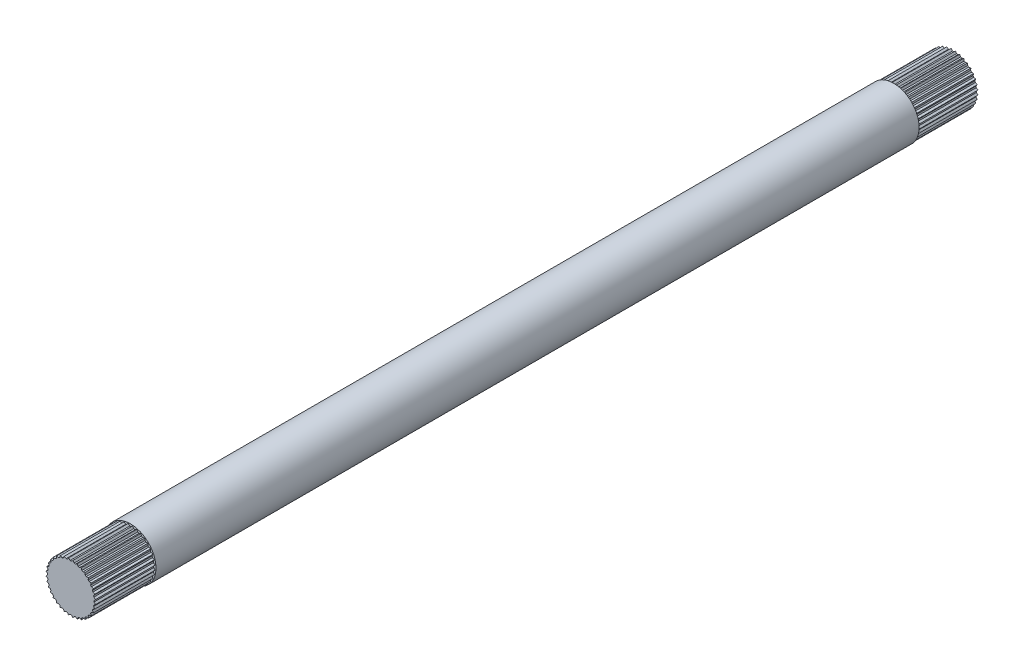
SolidWorks part; units mm, degrees
material "AISI 1015 Steel, Cold Drawn (SS)"
ref_plane "X-Y Datum" through (0, 0, 0) normal (0, 0, 1) x (1, 0, 0)
ref_plane "X-Z Datum" through (0, 0, 0) normal (0, 1, 0) x (1, 0, 0)
ref_plane "Y-Z Datum" through (0, 0, 0) normal (1, 0, 0) x (0, 0, -1)
sketch "Sketch9" plane through (0, 0, 0) normal (0, 1, 0) x (1, 0, 0)
  line L0 (16.002, 0) -> (0, 0)
  line L1 (0, 0) -> (0, -389.0916)
  line L2 (0, -389.0916) -> (-72.2493, -524.9728)
  dimension "D1" = 153.895
  dimension "D2" = 28
  dimension "D3" = 389.0916
  dimension "D5" = 16.002
sketch "Sketch5" plane through (0, 0, 0) normal (0, 1, 0) x (1, 0, 0)
  line L0 (7.9375, -350.9916) -> (7.9375, -22.1615)
  line L1 (7.9375, -22.1615) -> (9.525, -22.1615)
  line L2 (9.525, -22.1615) -> (9.525, -350.9916)
  line L3 (9.525, -350.9916) -> (7.9375, -350.9916)
  line L5 (16.002, 0) -> (0, 0) construction
  line L6 (0, 0) -> (0, -389.0916) construction
  line L7 (0, -389.0916) -> (9.525, -389.0916) construction
  line L8 (12.5602, -369.8416) -> (0, -369.8416) construction
  dimension "D1" = 1.5875
  dimension "D2" = 22.1615
  dimension "D3" = 7.9375
  dimension "D4" = 19.25
  dimension "D5" = 38.1
revolve "Revolve2" add sketch "Sketch5" angle 360 about L1
sketch "Sketch6" plane through (0, 0, 0) normal (0, 1, 0) x (1, 0, 0)
  circle A0 centre (0, -33.1635) radius 1.5875 construction
  circle A1 centre (0, -33.1635) radius 1.5875
sketch "Sketch7" plane through (0, 0, 0) normal (1, 0, 0) x (0, 0, -1)
  circle A2 centre (-39.196, 0) radius 1.5875
  circle A4 centre (-39.196, 0) radius 1.5875 construction
extrude "Cut-Extrude5" [suppressed] cut sketch "Sketch7" against normal through all both and the other way through all
extrude "Cut-Extrude6" [suppressed] cut sketch "Sketch6" against normal through all both and the other way through all
sketch "Sketch8" plane through (0, 0, 0) normal (0, 0, 1) x (1, 0, 0)
  line L0 (9.2357, -0.808) -> (8.6817, -0.254)
  line L1 (8.6817, -0.254) -> (8.6817, 0.254)
  line L2 (8.6817, 0.254) -> (9.2357, 0.808)
  line L3 (8.6817, 0) -> (0, 0) construction
  line L4 (8.9551, -2.3995) -> (8.5057, -1.7577)
  line L5 (8.5057, -1.7577) -> (8.5939, -1.2574)
  line L6 (8.5939, -1.2574) -> (9.2357, -0.808)
  line L7 (8.4024, -3.9181) -> (8.0713, -3.208)
  line L8 (8.0713, -3.208) -> (8.245, -2.7306)
  line L9 (8.245, -2.7306) -> (8.9551, -2.3995)
  line L10 (7.5944, -5.3176) -> (7.3916, -4.5608)
  line L11 (7.3916, -4.5608) -> (7.6456, -4.1209)
  line L12 (7.6456, -4.1209) -> (8.4024, -3.9181)
  line L13 (6.5556, -6.5556) -> (6.4873, -5.7751)
  line L14 (6.4873, -5.7751) -> (6.8138, -5.3859)
  line L15 (6.8138, -5.3859) -> (7.5944, -5.3176)
  line L16 (5.3176, -7.5944) -> (5.3859, -6.8138)
  line L17 (5.3859, -6.8138) -> (5.7751, -6.4873)
  line L18 (5.7751, -6.4873) -> (6.5556, -6.5556)
  line L19 (3.9181, -8.4024) -> (4.1209, -7.6456)
  line L20 (4.1209, -7.6456) -> (4.5608, -7.3916)
  line L21 (4.5608, -7.3916) -> (5.3176, -7.5944)
  line L22 (2.3995, -8.9551) -> (2.7306, -8.245)
  line L23 (2.7306, -8.245) -> (3.208, -8.0713)
  line L24 (3.208, -8.0713) -> (3.9181, -8.4024)
  line L25 (0.808, -9.2357) -> (1.2574, -8.5939)
  line L26 (1.2574, -8.5939) -> (1.7577, -8.5057)
  line L27 (1.7577, -8.5057) -> (2.3995, -8.9551)
  line L28 (-0.808, -9.2357) -> (-0.254, -8.6817)
  line L29 (-0.254, -8.6817) -> (0.254, -8.6817)
  line L30 (0.254, -8.6817) -> (0.808, -9.2357)
  line L31 (-2.3995, -8.9551) -> (-1.7577, -8.5057)
  line L32 (-1.7577, -8.5057) -> (-1.2574, -8.5939)
  line L33 (-1.2574, -8.5939) -> (-0.808, -9.2357)
  line L34 (-3.9181, -8.4024) -> (-3.208, -8.0713)
  line L35 (-3.208, -8.0713) -> (-2.7306, -8.245)
  line L36 (-2.7306, -8.245) -> (-2.3995, -8.9551)
  line L37 (-5.3176, -7.5944) -> (-4.5608, -7.3916)
  line L38 (-4.5608, -7.3916) -> (-4.1209, -7.6456)
  line L39 (-4.1209, -7.6456) -> (-3.9181, -8.4024)
  line L40 (-6.5556, -6.5556) -> (-5.7751, -6.4873)
  line L41 (-5.7751, -6.4873) -> (-5.3859, -6.8138)
  line L42 (-5.3859, -6.8138) -> (-5.3176, -7.5944)
  line L43 (-7.5944, -5.3176) -> (-6.8138, -5.3859)
  line L44 (-6.8138, -5.3859) -> (-6.4873, -5.7751)
  line L45 (-6.4873, -5.7751) -> (-6.5556, -6.5556)
  line L46 (-8.4024, -3.9181) -> (-7.6456, -4.1209)
  line L47 (-7.6456, -4.1209) -> (-7.3916, -4.5608)
  line L48 (-7.3916, -4.5608) -> (-7.5944, -5.3176)
  line L49 (-8.9551, -2.3995) -> (-8.245, -2.7306)
  line L50 (-8.245, -2.7306) -> (-8.0713, -3.208)
  line L51 (-8.0713, -3.208) -> (-8.4024, -3.9181)
  line L52 (-9.2357, -0.808) -> (-8.5939, -1.2574)
  line L53 (-8.5939, -1.2574) -> (-8.5057, -1.7577)
  line L54 (-8.5057, -1.7577) -> (-8.9551, -2.3995)
  line L55 (-9.2357, 0.808) -> (-8.6817, 0.254)
  line L56 (-8.6817, 0.254) -> (-8.6817, -0.254)
  line L57 (-8.6817, -0.254) -> (-9.2357, -0.808)
  line L58 (-8.9551, 2.3995) -> (-8.5057, 1.7577)
  line L59 (-8.5057, 1.7577) -> (-8.5939, 1.2574)
  line L60 (-8.5939, 1.2574) -> (-9.2357, 0.808)
  line L61 (-8.4024, 3.9181) -> (-8.0713, 3.208)
  line L62 (-8.0713, 3.208) -> (-8.245, 2.7306)
  line L63 (-8.245, 2.7306) -> (-8.9551, 2.3995)
  line L64 (-7.5944, 5.3176) -> (-7.3916, 4.5608)
  line L65 (-7.3916, 4.5608) -> (-7.6456, 4.1209)
  line L66 (-7.6456, 4.1209) -> (-8.4024, 3.9181)
  line L67 (-6.5556, 6.5556) -> (-6.4873, 5.7751)
  line L68 (-6.4873, 5.7751) -> (-6.8138, 5.3859)
  line L69 (-6.8138, 5.3859) -> (-7.5944, 5.3176)
  line L70 (-5.3176, 7.5944) -> (-5.3859, 6.8138)
  line L71 (-5.3859, 6.8138) -> (-5.7751, 6.4873)
  line L72 (-5.7751, 6.4873) -> (-6.5556, 6.5556)
  line L73 (-3.9181, 8.4024) -> (-4.1209, 7.6456)
  line L74 (-4.1209, 7.6456) -> (-4.5608, 7.3916)
  line L75 (-4.5608, 7.3916) -> (-5.3176, 7.5944)
  line L76 (-2.3995, 8.9551) -> (-2.7306, 8.245)
  line L77 (-2.7306, 8.245) -> (-3.208, 8.0713)
  line L78 (-3.208, 8.0713) -> (-3.9181, 8.4024)
  line L79 (-0.808, 9.2357) -> (-1.2574, 8.5939)
  line L80 (-1.2574, 8.5939) -> (-1.7577, 8.5057)
  line L81 (-1.7577, 8.5057) -> (-2.3995, 8.9551)
  line L82 (0.808, 9.2357) -> (0.254, 8.6817)
  line L83 (0.254, 8.6817) -> (-0.254, 8.6817)
  line L84 (-0.254, 8.6817) -> (-0.808, 9.2357)
  line L85 (2.3995, 8.9551) -> (1.7577, 8.5057)
  line L86 (1.7577, 8.5057) -> (1.2574, 8.5939)
  line L87 (1.2574, 8.5939) -> (0.808, 9.2357)
  line L88 (3.9181, 8.4024) -> (3.208, 8.0713)
  line L89 (3.208, 8.0713) -> (2.7306, 8.245)
  line L90 (2.7306, 8.245) -> (2.3995, 8.9551)
  line L91 (5.3176, 7.5944) -> (4.5608, 7.3916)
  line L92 (4.5608, 7.3916) -> (4.1209, 7.6456)
  line L93 (4.1209, 7.6456) -> (3.9181, 8.4024)
  line L94 (6.5556, 6.5556) -> (5.7751, 6.4873)
  line L95 (5.7751, 6.4873) -> (5.3859, 6.8138)
  line L96 (5.3859, 6.8138) -> (5.3176, 7.5944)
  line L97 (7.5944, 5.3176) -> (6.8138, 5.3859)
  line L98 (6.8138, 5.3859) -> (6.4873, 5.7751)
  line L99 (6.4873, 5.7751) -> (6.5556, 6.5556)
  line L100 (8.4024, 3.9181) -> (7.6456, 4.1209)
  line L101 (7.6456, 4.1209) -> (7.3916, 4.5608)
  line L102 (7.3916, 4.5608) -> (7.5944, 5.3176)
  line L103 (8.9551, 2.3995) -> (8.245, 2.7306)
  line L104 (8.245, 2.7306) -> (8.0713, 3.208)
  line L105 (8.0713, 3.208) -> (8.4024, 3.9181)
  line L106 (9.2357, 0.808) -> (8.5939, 1.2574)
  line L107 (8.5939, 1.2574) -> (8.5057, 1.7577)
  line L108 (8.5057, 1.7577) -> (8.9551, 2.3995)
  circle A0 centre (0, 0) radius 12.7
  circle A1 centre (0, 0) radius 9.271 construction
  circle A2 centre (0, 0) radius 8.6854 construction
  point P153 (0, 0)
  dimension "D1" = 25.4
  dimension "D4" = 18.542
  dimension "D6" = 17.3708
  dimension "D2" = 0.508
  dimension "D3" = 135
  dimension "D5" = 36
extrude "Cut-Extrude7" cut sketch "Sketch8" against normal blind 22.225 from surface starting at face at (-9.525, 0, 350.9916)
ref_plane "Plane1" through (0, 0, 47.5615) normal (0, 0, -1) x (-1, 0, 0)
sketch "Sketch10" plane through (0, 0, 47.5615) normal (0, 0, -1) x (-1, 0, 0)
  circle A0 centre (0, 0) radius 7.9375
  dimension "D1" = 15.875
extrude "Boss-Extrude1" add sketch "Sketch10" against normal up to surface (303.4301 mm away) up to face at (-7.9375, 0, 350.9916)
sketch "Sketch11" plane through (0, 0, 22.1615) normal (0, 0, -1) x (-1, 0, 0)
  line L0 (0, 9.525) -> (13.3548, 9.525) construction
  line L1 (0, 9.525) -> (0, 15.4312) construction
  line L2 (-9.525, 0) -> (-9.525, 9.1744) construction
  line L3 (-9.525, 0) -> (-16.674, 0) construction
  circle A0 centre (0, 0) radius 9.525 construction
  point P0 (0, 9.525)
  point P1 (-9.525, 0)
sketch "Sketch12" plane through (0, 0, 0) normal (0, 0, 1) x (1, 0, 0)
  line L0 (9.2357, -0.808) -> (8.6817, -0.254)
  line L1 (8.6817, -0.254) -> (8.6817, 0.254)
  line L2 (8.6817, 0.254) -> (9.2357, 0.808)
  line L3 (8.6817, 0) -> (0, 0) construction
  line L4 (8.9551, -2.3995) -> (8.5057, -1.7577)
  line L5 (8.5057, -1.7577) -> (8.5939, -1.2574)
  line L6 (8.5939, -1.2574) -> (9.2357, -0.808)
  line L7 (8.4024, -3.9181) -> (8.0713, -3.208)
  line L8 (8.0713, -3.208) -> (8.245, -2.7306)
  line L9 (8.245, -2.7306) -> (8.9551, -2.3995)
  line L10 (7.5944, -5.3176) -> (7.3916, -4.5608)
  line L11 (7.3916, -4.5608) -> (7.6456, -4.1209)
  line L12 (7.6456, -4.1209) -> (8.4024, -3.9181)
  line L13 (6.5556, -6.5556) -> (6.4873, -5.7751)
  line L14 (6.4873, -5.7751) -> (6.8138, -5.3859)
  line L15 (6.8138, -5.3859) -> (7.5944, -5.3176)
  line L16 (5.3176, -7.5944) -> (5.3859, -6.8138)
  line L17 (5.3859, -6.8138) -> (5.7751, -6.4873)
  line L18 (5.7751, -6.4873) -> (6.5556, -6.5556)
  line L19 (3.9181, -8.4024) -> (4.1209, -7.6456)
  line L20 (4.1209, -7.6456) -> (4.5608, -7.3916)
  line L21 (4.5608, -7.3916) -> (5.3176, -7.5944)
  line L22 (2.3995, -8.9551) -> (2.7306, -8.245)
  line L23 (2.7306, -8.245) -> (3.208, -8.0713)
  line L24 (3.208, -8.0713) -> (3.9181, -8.4024)
  line L25 (0.808, -9.2357) -> (1.2574, -8.5939)
  line L26 (1.2574, -8.5939) -> (1.7577, -8.5057)
  line L27 (1.7577, -8.5057) -> (2.3995, -8.9551)
  line L28 (-0.808, -9.2357) -> (-0.254, -8.6817)
  line L29 (-0.254, -8.6817) -> (0.254, -8.6817)
  line L30 (0.254, -8.6817) -> (0.808, -9.2357)
  line L31 (-2.3995, -8.9551) -> (-1.7577, -8.5057)
  line L32 (-1.7577, -8.5057) -> (-1.2574, -8.5939)
  line L33 (-1.2574, -8.5939) -> (-0.808, -9.2357)
  line L34 (-3.9181, -8.4024) -> (-3.208, -8.0713)
  line L35 (-3.208, -8.0713) -> (-2.7306, -8.245)
  line L36 (-2.7306, -8.245) -> (-2.3995, -8.9551)
  line L37 (-5.3176, -7.5944) -> (-4.5608, -7.3916)
  line L38 (-4.5608, -7.3916) -> (-4.1209, -7.6456)
  line L39 (-4.1209, -7.6456) -> (-3.9181, -8.4024)
  line L40 (-6.5556, -6.5556) -> (-5.7751, -6.4873)
  line L41 (-5.7751, -6.4873) -> (-5.3859, -6.8138)
  line L42 (-5.3859, -6.8138) -> (-5.3176, -7.5944)
  line L43 (-7.5944, -5.3176) -> (-6.8138, -5.3859)
  line L44 (-6.8138, -5.3859) -> (-6.4873, -5.7751)
  line L45 (-6.4873, -5.7751) -> (-6.5556, -6.5556)
  line L46 (-8.4024, -3.9181) -> (-7.6456, -4.1209)
  line L47 (-7.6456, -4.1209) -> (-7.3916, -4.5608)
  line L48 (-7.3916, -4.5608) -> (-7.5944, -5.3176)
  line L49 (-8.9551, -2.3995) -> (-8.245, -2.7306)
  line L50 (-8.245, -2.7306) -> (-8.0713, -3.208)
  line L51 (-8.0713, -3.208) -> (-8.4024, -3.9181)
  line L52 (-9.2357, -0.808) -> (-8.5939, -1.2574)
  line L53 (-8.5939, -1.2574) -> (-8.5057, -1.7577)
  line L54 (-8.5057, -1.7577) -> (-8.9551, -2.3995)
  line L55 (-9.2357, 0.808) -> (-8.6817, 0.254)
  line L56 (-8.6817, 0.254) -> (-8.6817, -0.254)
  line L57 (-8.6817, -0.254) -> (-9.2357, -0.808)
  line L58 (-8.9551, 2.3995) -> (-8.5057, 1.7577)
  line L59 (-8.5057, 1.7577) -> (-8.5939, 1.2574)
  line L60 (-8.5939, 1.2574) -> (-9.2357, 0.808)
  line L61 (-8.4024, 3.9181) -> (-8.0713, 3.208)
  line L62 (-8.0713, 3.208) -> (-8.245, 2.7306)
  line L63 (-8.245, 2.7306) -> (-8.9551, 2.3995)
  line L64 (-7.5944, 5.3176) -> (-7.3916, 4.5608)
  line L65 (-7.3916, 4.5608) -> (-7.6456, 4.1209)
  line L66 (-7.6456, 4.1209) -> (-8.4024, 3.9181)
  line L67 (-6.5556, 6.5556) -> (-6.4873, 5.7751)
  line L68 (-6.4873, 5.7751) -> (-6.8138, 5.3859)
  line L69 (-6.8138, 5.3859) -> (-7.5944, 5.3176)
  line L70 (-5.3176, 7.5944) -> (-5.3859, 6.8138)
  line L71 (-5.3859, 6.8138) -> (-5.7751, 6.4873)
  line L72 (-5.7751, 6.4873) -> (-6.5556, 6.5556)
  line L73 (-3.9181, 8.4024) -> (-4.1209, 7.6456)
  line L74 (-4.1209, 7.6456) -> (-4.5608, 7.3916)
  line L75 (-4.5608, 7.3916) -> (-5.3176, 7.5944)
  line L76 (-2.3995, 8.9551) -> (-2.7306, 8.245)
  line L77 (-2.7306, 8.245) -> (-3.208, 8.0713)
  line L78 (-3.208, 8.0713) -> (-3.9181, 8.4024)
  line L79 (-0.808, 9.2357) -> (-1.2574, 8.5939)
  line L80 (-1.2574, 8.5939) -> (-1.7577, 8.5057)
  line L81 (-1.7577, 8.5057) -> (-2.3995, 8.9551)
  line L82 (0.808, 9.2357) -> (0.254, 8.6817)
  line L83 (0.254, 8.6817) -> (-0.254, 8.6817)
  line L84 (-0.254, 8.6817) -> (-0.808, 9.2357)
  line L85 (2.3995, 8.9551) -> (1.7577, 8.5057)
  line L86 (1.7577, 8.5057) -> (1.2574, 8.5939)
  line L87 (1.2574, 8.5939) -> (0.808, 9.2357)
  line L88 (3.9181, 8.4024) -> (3.208, 8.0713)
  line L89 (3.208, 8.0713) -> (2.7306, 8.245)
  line L90 (2.7306, 8.245) -> (2.3995, 8.9551)
  line L91 (5.3176, 7.5944) -> (4.5608, 7.3916)
  line L92 (4.5608, 7.3916) -> (4.1209, 7.6456)
  line L93 (4.1209, 7.6456) -> (3.9181, 8.4024)
  line L94 (6.5556, 6.5556) -> (5.7751, 6.4873)
  line L95 (5.7751, 6.4873) -> (5.3859, 6.8138)
  line L96 (5.3859, 6.8138) -> (5.3176, 7.5944)
  line L97 (7.5944, 5.3176) -> (6.8138, 5.3859)
  line L98 (6.8138, 5.3859) -> (6.4873, 5.7751)
  line L99 (6.4873, 5.7751) -> (6.5556, 6.5556)
  line L100 (8.4024, 3.9181) -> (7.6456, 4.1209)
  line L101 (7.6456, 4.1209) -> (7.3916, 4.5608)
  line L102 (7.3916, 4.5608) -> (7.5944, 5.3176)
  line L103 (8.9551, 2.3995) -> (8.245, 2.7306)
  line L104 (8.245, 2.7306) -> (8.0713, 3.208)
  line L105 (8.0713, 3.208) -> (8.4024, 3.9181)
  line L106 (9.2357, 0.808) -> (8.5939, 1.2574)
  line L107 (8.5939, 1.2574) -> (8.5057, 1.7577)
  line L108 (8.5057, 1.7577) -> (8.9551, 2.3995)
  circle A0 centre (0, 0) radius 12.7
  circle A1 centre (0, 0) radius 9.271 construction
  circle A2 centre (0, 0) radius 8.6854 construction
  point P153 (0, 0)
  dimension "D1" = 25.4
  dimension "D4" = 18.542
  dimension "D6" = 17.3708
  dimension "D2" = 0.508
  dimension "D3" = 135
  dimension "D5" = 36
extrude "Cut-Extrude8" cut sketch "Sketch12" along normal blind 22.225 from surface starting at face at (-7.9375, 0, 22.1615)
